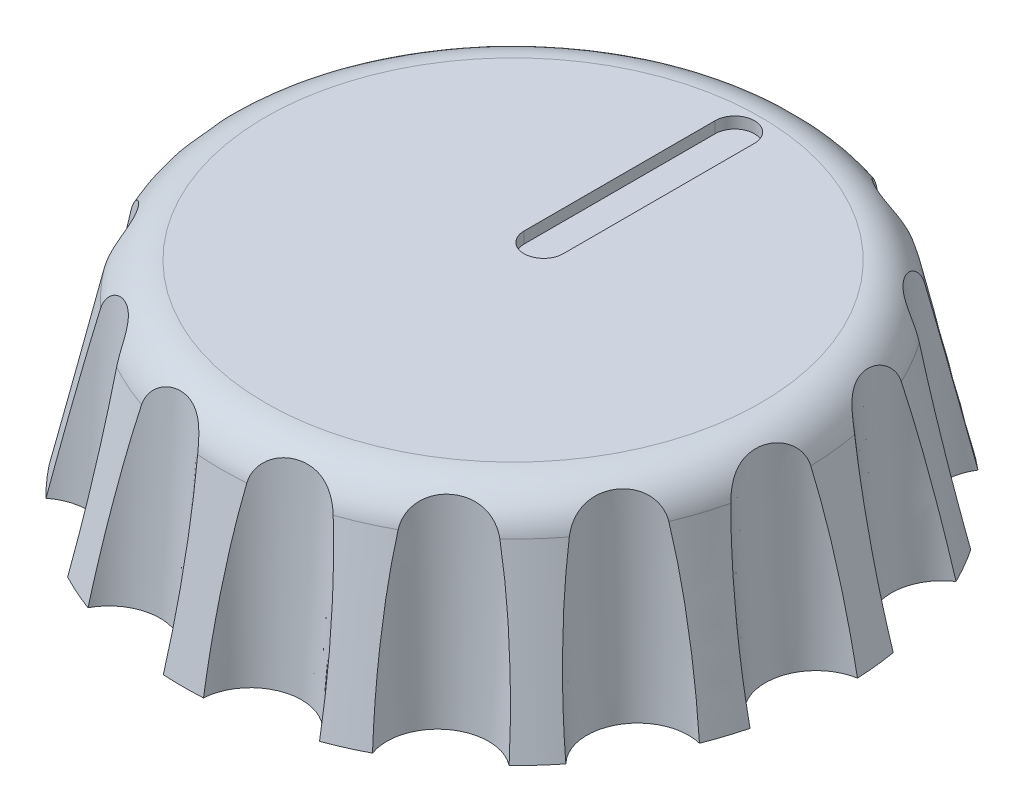
SolidWorks part; units mm, degrees
ref_plane "Front Plane" through (0, 0, 0) normal (0, 0, 1) x (1, 0, 0)
ref_plane "Top Plane" through (0, 0, 0) normal (0, 1, 0) x (1, 0, 0)
ref_plane "Right Plane" through (0, 0, 0) normal (1, 0, 0) x (0, 0, -1)
sketch "Sketch1" plane through (0, 0, 0) normal (0, 1, 0) x (1, 0, 0)
  circle A0 centre (0, 0) radius 15
extrude "Boss-Extrude1" add sketch "Sketch1" along normal blind 11
sketch "Sketch2" plane through (0, 0, 0) normal (0, -1, 0) x (1, 0, 0)
  circle A0 centre (0, 0) radius 2.95
extrude "Cut-Extrude1" cut sketch "Sketch2" against normal blind 9.8
sketch "Sketch3" plane through (0, 0, 0) normal (0, 1, 0) x (1, 0, 0)
  line L3 (0.5, 2.8837) -> (-0.5, 2.8837)
  line L4 (-0.5, 2.8837) -> (0, 3.3837)
  line L5 (0, 3.3837) -> (0.5, 2.8837)
  line L6 (0, 0) -> (0, 1.3989) construction
  line L7 (0, 0) -> (-1.6482, 0) construction
  line L8 (1.4561, 2.5388) -> (0.5164, 2.8808)
  line L9 (0.5164, 2.8808) -> (1.1573, 3.1796)
  line L10 (1.1573, 3.1796) -> (1.4561, 2.5388)
  line L11 (0, 0) -> (0.4785, 1.3146) construction
  line L12 (0, 0) -> (-1.5488, 0.5637) construction
  line L13 (2.2366, 1.8876) -> (1.4706, 2.5304)
  line L14 (1.4706, 2.5304) -> (2.175, 2.592)
  line L15 (2.175, 2.592) -> (2.2366, 1.8876)
  line L16 (0, 0) -> (0.8992, 1.0716) construction
  line L17 (0, 0) -> (-1.2626, 1.0594) construction
  line L18 (2.7473, 1.0088) -> (2.2473, 1.8749)
  line L19 (2.2473, 1.8749) -> (2.9304, 1.6918)
  line L20 (2.9304, 1.6918) -> (2.7473, 1.0088)
  line L21 (0, 0) -> (1.2115, 0.6995) construction
  line L22 (0, 0) -> (-0.8241, 1.4274) construction
  line L23 (2.9267, 0.0083) -> (2.753, 0.9931)
  line L24 (2.753, 0.9931) -> (3.3323, 0.5876)
  line L25 (3.3323, 0.5876) -> (2.9267, 0.0083)
  line L26 (0, 0) -> (1.3777, 0.2429) construction
  line L27 (0, 0) -> (-0.2862, 1.6231) construction
  line L28 (2.753, -0.9931) -> (2.9267, -0.0083)
  line L29 (2.9267, -0.0083) -> (3.3323, -0.5876)
  line L30 (3.3323, -0.5876) -> (2.753, -0.9931)
  line L31 (0, 0) -> (1.3777, -0.2429) construction
  line L32 (0, 0) -> (0.2862, 1.6231) construction
  line L33 (2.2473, -1.8749) -> (2.7473, -1.0088)
  line L34 (2.7473, -1.0088) -> (2.9304, -1.6918)
  line L35 (2.9304, -1.6918) -> (2.2473, -1.8749)
  line L36 (0, 0) -> (1.2115, -0.6995) construction
  line L37 (0, 0) -> (0.8241, 1.4274) construction
  line L38 (1.4706, -2.5304) -> (2.2366, -1.8876)
  line L39 (2.2366, -1.8876) -> (2.175, -2.592)
  line L40 (2.175, -2.592) -> (1.4706, -2.5304)
  line L41 (0, 0) -> (0.8992, -1.0716) construction
  line L42 (0, 0) -> (1.2626, 1.0594) construction
  line L43 (0.5164, -2.8808) -> (1.4561, -2.5388)
  line L44 (1.4561, -2.5388) -> (1.1573, -3.1796)
  line L45 (1.1573, -3.1796) -> (0.5164, -2.8808)
  line L46 (0, 0) -> (0.4785, -1.3146) construction
  line L47 (0, 0) -> (1.5488, 0.5637) construction
  line L48 (-0.5, -2.8837) -> (0.5, -2.8837)
  line L49 (0.5, -2.8837) -> (0, -3.3837)
  line L50 (0, -3.3837) -> (-0.5, -2.8837)
  line L51 (0, 0) -> (0, -1.3989) construction
  line L52 (0, 0) -> (1.6482, 0) construction
  line L53 (-1.4561, -2.5388) -> (-0.5164, -2.8808)
  line L54 (-0.5164, -2.8808) -> (-1.1573, -3.1796)
  line L55 (-1.1573, -3.1796) -> (-1.4561, -2.5388)
  line L56 (0, 0) -> (-0.4785, -1.3146) construction
  line L57 (0, 0) -> (1.5488, -0.5637) construction
  line L58 (-2.2366, -1.8876) -> (-1.4706, -2.5304)
  line L59 (-1.4706, -2.5304) -> (-2.175, -2.592)
  line L60 (-2.175, -2.592) -> (-2.2366, -1.8876)
  line L61 (0, 0) -> (-0.8992, -1.0716) construction
  line L62 (0, 0) -> (1.2626, -1.0594) construction
  line L63 (-2.7473, -1.0088) -> (-2.2473, -1.8749)
  line L64 (-2.2473, -1.8749) -> (-2.9304, -1.6918)
  line L65 (-2.9304, -1.6918) -> (-2.7473, -1.0088)
  line L66 (0, 0) -> (-1.2115, -0.6995) construction
  line L67 (0, 0) -> (0.8241, -1.4274) construction
  line L68 (-2.9267, -0.0083) -> (-2.753, -0.9931)
  line L69 (-2.753, -0.9931) -> (-3.3323, -0.5876)
  line L70 (-3.3323, -0.5876) -> (-2.9267, -0.0083)
  line L71 (0, 0) -> (-1.3777, -0.2429) construction
  line L72 (0, 0) -> (0.2862, -1.6231) construction
  line L73 (-2.753, 0.9931) -> (-2.9267, 0.0083)
  line L74 (-2.9267, 0.0083) -> (-3.3323, 0.5876)
  line L75 (-3.3323, 0.5876) -> (-2.753, 0.9931)
  line L76 (0, 0) -> (-1.3777, 0.2429) construction
  line L77 (0, 0) -> (-0.2862, -1.6231) construction
  line L78 (-2.2473, 1.8749) -> (-2.7473, 1.0088)
  line L79 (-2.7473, 1.0088) -> (-2.9304, 1.6918)
  line L80 (-2.9304, 1.6918) -> (-2.2473, 1.8749)
  line L81 (0, 0) -> (-1.2115, 0.6995) construction
  line L82 (0, 0) -> (-0.8241, -1.4274) construction
  line L83 (-1.4706, 2.5304) -> (-2.2366, 1.8876)
  line L84 (-2.2366, 1.8876) -> (-2.175, 2.592)
  line L85 (-2.175, 2.592) -> (-1.4706, 2.5304)
  line L86 (0, 0) -> (-0.8992, 1.0716) construction
  line L87 (0, 0) -> (-1.2626, -1.0594) construction
  line L88 (-0.5164, 2.8808) -> (-1.4561, 2.5388)
  line L89 (-1.4561, 2.5388) -> (-1.1573, 3.1796)
  line L90 (-1.1573, 3.1796) -> (-0.5164, 2.8808)
  line L91 (0, 0) -> (-0.4785, 1.3146) construction
  line L92 (0, 0) -> (-1.5488, -0.5637) construction
  point P95 (0, 0)
  dimension "D1" = 18
extrude "Cut-Extrude2" cut sketch "Sketch3" along normal blind 9.8
chamfer "Chamfer1" distance 11 distance2 2.5 1 edges at (0, 11, 15) first distance on face at (0, 11, 15)
sketch "Sketch4" plane through (0, 0, 0) normal (0, 1, 0) x (1, 0, 0)
  line L0 (0, 0) -> (0, 8.2706) construction
  line L1 (0, 0) -> (8.2394, 0) construction
  line L2 (0, 0) -> (3.3639, 7.5555) construction
  line L3 (0, 0) -> (7.5271, -3.3513) construction
  line L4 (0, 0) -> (6.1462, 5.5341) construction
  line L5 (0, 0) -> (5.5132, -6.1231) construction
  line L6 (0, 0) -> (7.8658, 2.5557) construction
  line L7 (0, 0) -> (2.5461, -7.8361) construction
  line L8 (0, 0) -> (8.2253, -0.8645) construction
  line L9 (0, 0) -> (-0.8613, -8.1943) construction
  line L10 (0, 0) -> (7.1625, -4.1353) construction
  line L11 (0, 0) -> (-4.1197, -7.1355) construction
  line L12 (0, 0) -> (4.8613, -6.691) construction
  line L13 (0, 0) -> (-6.6658, -4.843) construction
  line L14 (0, 0) -> (1.7195, -8.0898) construction
  line L15 (0, 0) -> (-8.0593, -1.7131) construction
  line L16 (0, 0) -> (-1.7195, -8.0898) construction
  line L17 (0, 0) -> (-8.0593, 1.7131) construction
  line L18 (0, 0) -> (-4.8613, -6.691) construction
  line L19 (0, 0) -> (-6.6658, 4.843) construction
  line L20 (0, 0) -> (-7.1625, -4.1353) construction
  line L21 (0, 0) -> (-4.1197, 7.1355) construction
  line L22 (0, 0) -> (-8.2253, -0.8645) construction
  line L23 (0, 0) -> (-0.8613, 8.1943) construction
  line L24 (0, 0) -> (-7.8658, 2.5557) construction
  line L25 (0, 0) -> (2.5461, 7.8361) construction
  line L26 (0, 0) -> (-6.1462, 5.5341) construction
  line L27 (0, 0) -> (5.5132, 6.1231) construction
  line L28 (0, 0) -> (-3.3639, 7.5555) construction
  line L29 (0, 0) -> (7.5271, 3.3513) construction
  circle A21 centre (0, 15) radius 2.1
  circle A22 centre (0, 0) radius 15 construction
  circle A23 centre (6.101, 13.7032) radius 2.1
  circle A24 centre (11.1472, 10.037) radius 2.1
  circle A25 centre (14.2658, 4.6353) radius 2.1
  circle A26 centre (14.9178, -1.5679) radius 2.1
  circle A27 centre (12.9904, -7.5) radius 2.1
  circle A28 centre (8.8168, -12.1353) radius 2.1
  circle A29 centre (3.1187, -14.6722) radius 2.1
  circle A30 centre (-3.1187, -14.6722) radius 2.1
  circle A31 centre (-8.8168, -12.1353) radius 2.1
  circle A32 centre (-12.9904, -7.5) radius 2.1
  circle A33 centre (-14.9178, -1.5679) radius 2.1
  circle A34 centre (-14.2658, 4.6353) radius 2.1
  circle A35 centre (-11.1472, 10.037) radius 2.1
  circle A36 centre (-6.101, 13.7032) radius 2.1
  point P66 (0, 0)
fillet "Fillet1" radius 2 1 edges at (0, 11, 12.5)
sketch "Sketch5" plane through (0, 11, 0) normal (0, 1, 0) x (1, 0, 0)
  line L0 (0, 1.3464) -> (0, 9.7652) construction
  line L1 (-0.8653, 1.3464) -> (-0.8653, 9.7652)
  line L2 (0.8653, 1.3464) -> (0.8653, 9.7652)
  arc A0 (-0.8653, 1.3464) -> (0.8653, 1.3464) centre (0, 1.3464) ccw
  arc A1 (0.8653, 9.7652) -> (-0.8653, 9.7652) centre (0, 9.7652) ccw
  point P3 (0, 5.5558)
extrude "Cut-Extrude6" cut sketch "Sketch5" against normal blind 0.5
extrude "Cut-Extrude7" cut sketch "Sketch4" along normal blind 11 draft 4 draft outward yes
sketch "Sketch6" plane through (0, 0, 0) normal (0, -1, 0) x (1, 0, 0)
  line L1 (-22.9771, -16.7841) -> (22.9771, -16.7841)
  line L2 (-22.9771, -16.7841) -> (-22.9771, 16.7841)
  line L3 (-22.9771, 16.7841) -> (22.9771, 16.7841)
  line L4 (22.9771, -16.7841) -> (22.9771, 16.7841)
  line L5 (-22.9771, -16.7841) -> (22.9771, 16.7841) construction
  line L6 (-22.9771, 16.7841) -> (22.9771, -16.7841) construction
  point P0 (0, 0)
extrude "Cut-Extrude8" cut sketch "Sketch6" against normal blind 2
